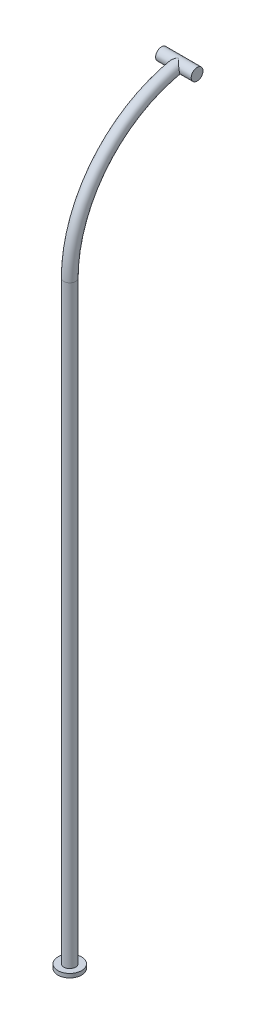
SolidWorks part; units mm, degrees
material "Nylon 101"
ref_plane "Front Plane" through (0, 0, 0) normal (0, 0, 1) x (1, 0, 0)
ref_plane "Top Plane" through (0, 0, 0) normal (0, 1, 0) x (1, 0, 0)
ref_plane "Right Plane" through (0, 0, 0) normal (1, 0, 0) x (0, 0, -1)
sketch "Sketch1" plane through (0, 0, 0) normal (0, 1, 0) x (1, 0, 0)
  circle A0 centre (0, 0) radius 1.5
extrude "Boss-Extrude1" add sketch "Sketch1" along normal blind 150
sketch "Sketch4" plane through (0, 0, 0) normal (0, -1, 0) x (1, 0, 0)
  circle A0 centre (0, 0) radius 3
extrude "Boss-Extrude4" add sketch "Sketch4" along normal blind 1
sketch "Sketch7" plane through (0, 150, 0) normal (0, 1, 0) x (1, 0, 0)
  line L0 (0, 0) -> (0, 44.3626) construction
  line L1 (0, 44.3626) -> (0, 33.5) construction
  line L2 (0, 33.5) -> (-42.5101, 33.5) construction
  line L3 (-42.5101, 33.5) -> (39.1951, 33.5) construction
  circle A0 centre (0, 0) radius 1.5
  dimension "D1" = 33.5
revolve "Revolve1" add sketch "Sketch7" angle 80 about L3 reverse direction yes
sketch "Sketch8" plane through (0, 0, 0) normal (1, 0, 0) x (0, 0, -1)
  line L0 (27.9433, 181.5138) -> (27.4223, 184.4683) construction
  circle A0 centre (27.6828, 182.9911) radius 1.5
extrude "Boss-Extrude5" add sketch "Sketch8" along normal blind 4.5 and the other way blind 4.5
equation "\"4.5.00mm\"=10"
